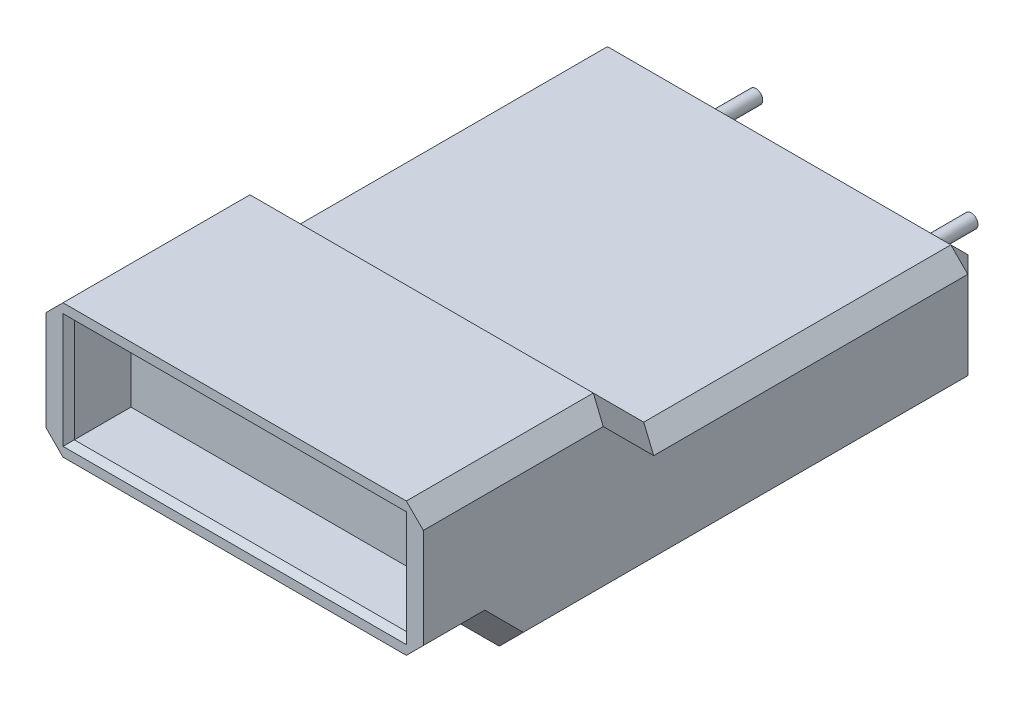
SolidWorks part; units mm, degrees
ref_plane "Front Plane" through (0, 0, 0) normal (0, 0, 1) x (1, 0, 0)
ref_plane "Top Plane" through (0, 0, 0) normal (0, 1, 0) x (1, 0, 0)
ref_plane "Right Plane" through (0, 0, 0) normal (1, 0, 0) x (0, 0, -1)
sketch "Sketch1" plane through (0, 0, 0) normal (1, 0, 0) x (0, 0, -1)
  line L0 (-24.775, 15.2) -> (-8.275, 15.2)
  line L1 (-8.275, 15.2) -> (-3.825, 10.75)
  line L2 (-3.825, 10.75) -> (24.775, 10.75)
  line L3 (24.775, 10.75) -> (24.775, 0)
  line L4 (24.775, 0) -> (-16.575, 0)
  line L5 (-16.575, 0) -> (-19.975, 3.4)
  line L6 (-19.975, 3.4) -> (-24.775, 3.4)
  line L7 (-24.775, 3.4) -> (-24.775, 15.2)
  line L8 (24.775, 0) -> (-24.775, 0) construction
  dimension "D1" = 11.8
  dimension "D2" = 10.75
  dimension "D3" = 4.8
  dimension "D4" = 16.5
  dimension "D5" = 8.2
  dimension "D6" = 28.6
  dimension "D7" = 15.2
extrude "Boss-Extrude1" add sketch "Sketch1" along normal blind 16.65 and the other way blind 16.65
chamfer "Chamfer1" distance 1.5 angle 45 16 edges at (-16.65, 5.375, -24.775) (-16.65, 3.4, 22.375) (-16.65, 1.7, 18.275) (-16.65, 0, -4.1) (0, 0, -24.775) (16.65, 3.4, 22.375) (16.65, 1.7, 18.275) (16.65, 0, -4.1) (16.65, 5.375, -24.775) (-16.65, 15.2, 16.525) (-16.65, 12.975, 6.05) (-16.65, 10.75, -10.475) (0, 10.75, -24.775) (16.65, 10.75, -10.475) (16.65, 12.975, 6.05) (16.65, 15.2, 16.525)
sketch "Sketch2" plane through (0, 0, -24.775) normal (0, 0, -1) x (-1, 0, 0)
  line L0 (-15.15, 6) -> (15.15, 6) construction
  line L1 (-15.15, 9.25) -> (-15.15, 1.5) construction
  line L2 (15.15, 1.5) -> (15.15, 9.25) construction
  line L3 (15.15, 0) -> (-15.15, 0) construction
  circle A0 centre (-9.45, 6) radius 1.75
  circle A1 centre (9.55, 6) radius 1.75
  dimension "D2" = 3.5
  dimension "D1" = 6
  dimension "D3" = 5.6
  dimension "D4" = 19
extrude "Boss-Extrude2" add sketch "Sketch2" along normal blind 1
sketch "Sketch3" plane through (0, 0, -25.775) normal (0, 0, -1) x (-1, 0, 0)
  circle A0 centre (-9.45, 6) radius 0.6
  circle A1 centre (9.55, 6) radius 0.6
  dimension "D1" = 1.2
extrude "Boss-Extrude3" add sketch "Sketch3" along normal blind 5
sketch "Sketch4" plane through (0, 0, 24.775) normal (0, 0, 1) x (1, 0, 0)
  line L0 (0, 0) -> (0, 18.7624) construction
  line L1 (-14.65, 13.875) -> (14.65, 13.875)
  line L2 (-14.65, 13.875) -> (-14.65, 4.725)
  line L3 (-14.65, 4.725) -> (14.65, 4.725)
  line L4 (14.65, 13.875) -> (14.65, 4.725)
  line L5 (-15.15, 0) -> (15.15, 0) construction
  line L6 (12.1703, 15.2) -> (12.1703, 13.875) construction
  line L7 (-15.15, 15.2) -> (15.15, 15.2) construction
  line L8 (13.9591, 4.725) -> (13.9591, 3.4) construction
  line L9 (-15.15, 3.4) -> (15.15, 3.4) construction
  point P8 (0, 13.875)
  dimension "D1" = 29.3
  dimension "D2" = 9.15
extrude "Cut-Extrude1" cut sketch "Sketch4" against normal blind 5.5
chamfer "Chamfer2" distance 0.5 angle 45 4 edges at (14.65, 9.3, 24.775) (0, 4.725, 24.775) (0, 13.875, 24.775) (-14.65, 9.3, 24.775)
